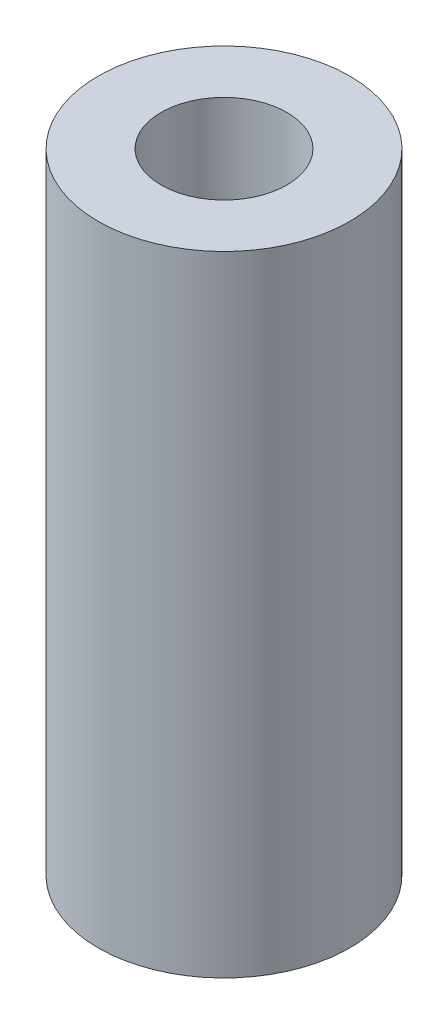
SolidWorks part; units mm, degrees
ref_plane "Front Plane" through (0, 0, 0) normal (0, 0, 1) x (1, 0, 0)
ref_plane "Top Plane" through (0, 0, 0) normal (0, 1, 0) x (1, 0, 0)
ref_plane "Right Plane" through (0, 0, 0) normal (1, 0, 0) x (0, 0, -1)
sketch "Sketch1" plane through (0, 0, 0) normal (0, 1, 0) x (1, 0, 0)
  circle A0 centre (0, 0) radius 50.8
  circle A1 centre (0, 0) radius 25.4
  dimension "D1" = 101.6
  dimension "D2" = 50.8
extrude "Boss-Extrude1" add sketch "Sketch1" along normal blind 254
equation "\"Body_Tube_OD\"= 4in"
equation "\"Body_Tube_ID\"= 2in"
equation "\"D1@Sketch1\"=\"Body_Tube_OD\""
equation "\"D2@Sketch1\"=\"Body_Tube_ID\""
equation "\"Fwd_Section_Length\" = 10in"
equation "\"D1@Boss-Extrude1\"=\"Fwd_Section_Length\""
